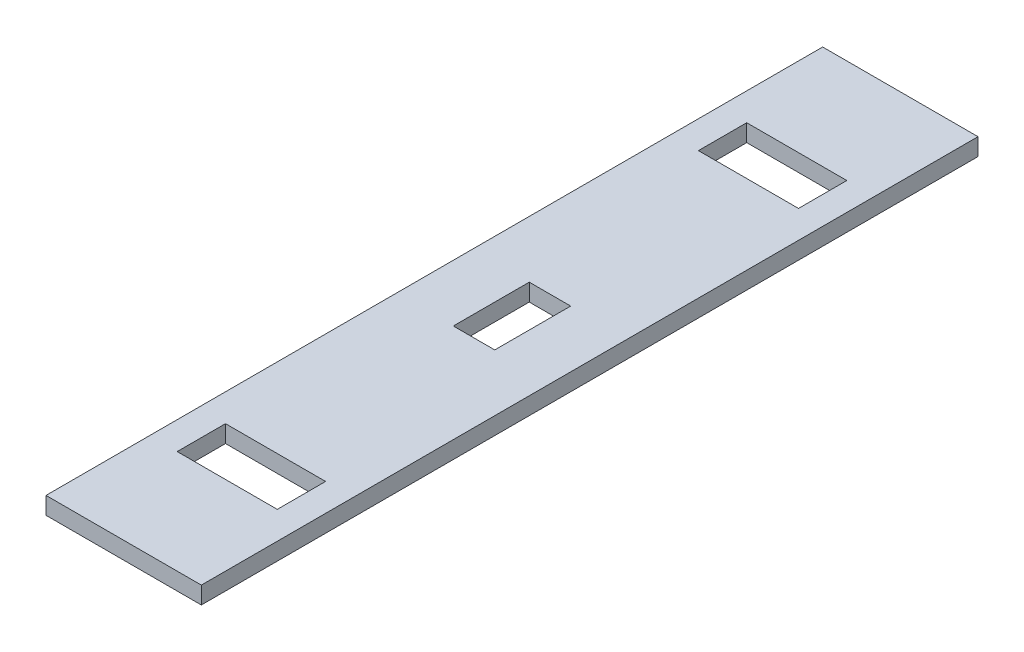
SolidWorks part; units mm, degrees
ref_plane "Plan de face" through (0, 0, 0) normal (0, 0, 1) x (1, 0, 0)
ref_plane "Plan de dessus" through (0, 0, 0) normal (0, 1, 0) x (1, 0, 0)
ref_plane "Plan de droite" through (0, 0, 0) normal (1, 0, 0) x (0, 0, -1)
sketch "Esquisse1" plane through (0, 0, 0) normal (0, 1, 0) x (1, 0, 0)
  line L0 (3.409, -1.8775) -> (3.409, 4.1225) construction
  line L1 (-1.091, 43.1225) -> (7.909, 43.1225)
  line L2 (-1.091, 43.1225) -> (-1.091, -1.8775)
  line L3 (-1.091, -1.8775) -> (7.909, -1.8775)
  line L4 (7.909, 43.1225) -> (7.909, -1.8775)
  line L5 (0.509, 4.1225) -> (6.309, 4.1225)
  line L6 (0.509, 4.1225) -> (0.509, 6.9225)
  line L7 (0.509, 6.9225) -> (6.309, 6.9225)
  line L8 (6.309, 4.1225) -> (6.309, 6.9225)
  line L9 (-1.091, 20.6225) -> (7.909, 20.6225) construction
  line L10 (0.509, 34.3225) -> (6.309, 34.3225)
  line L11 (6.309, 37.1225) -> (6.309, 34.3225)
  line L12 (0.509, 37.1225) -> (6.309, 37.1225)
  line L13 (0.509, 37.1225) -> (0.509, 34.3225)
  dimension "D1" = 45
  dimension "D2" = 9
  dimension "D3" = 6
  dimension "D4" = 5.8
  dimension "D5" = 2.8
extrude "Boss.-Extru.1" add sketch "Esquisse1" along normal blind 1 contours L4 L1 L2 L3 L13 L12 L11 L10 L8 L5 L6 L7 region at (3.409, 0, -20.6225)
sketch "Esquisse2" plane through (0, 0, 0) normal (0, -1, 0) x (1, 0, 0)
  line L0 (-1.091, -20.6225) -> (7.909, -20.6225) construction
  line L1 (-1.091, -43.1225) -> (-1.091, 1.8775) construction
  line L2 (7.909, -43.1225) -> (7.909, 1.8775) construction
  line L4 (4.609, -22.8225) -> (2.209, -22.8225)
  line L5 (4.609, -22.8225) -> (4.609, -18.4225)
  line L6 (4.609, -18.4225) -> (2.209, -18.4225)
  line L7 (2.209, -22.8225) -> (2.209, -18.4225)
  line L8 (4.609, -22.8225) -> (2.209, -18.4225) construction
  line L9 (4.609, -18.4225) -> (2.209, -22.8225) construction
  point P6 (3.409, -20.6225)
  point P11 (3.409, -20.6225)
  dimension "D1" = 4.4
  dimension "D2" = 2.4
extrude "Enlèv. mat.-Extru.1" cut sketch "Esquisse2" along normal through all and the other way through all contours L7 L4 L5 L6 region at (3.409, 0, -20.6225)
